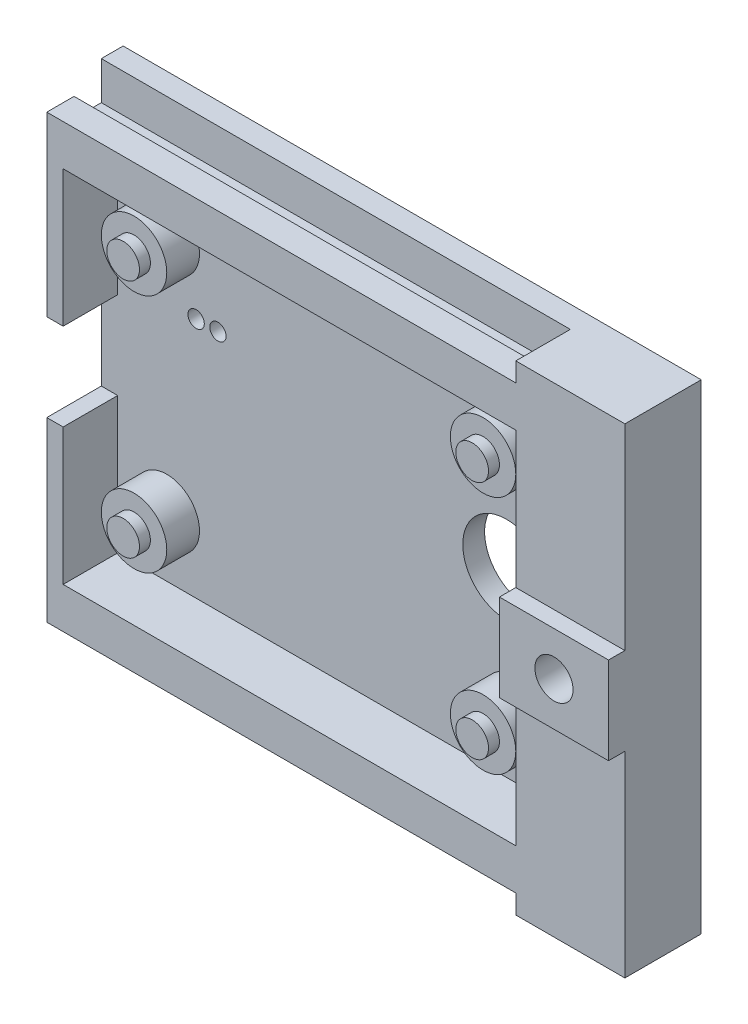
SolidWorks part; units mm, degrees
ref_plane "Alzado" through (0, 0, 0) normal (0, 0, 1) x (1, 0, 0)
ref_plane "Planta" through (0, 0, 0) normal (0, 1, 0) x (1, 0, 0)
ref_plane "Vista lateral" through (0, 0, 0) normal (1, 0, 0) x (0, 0, -1)
sketch "Croquis1" plane through (0, 0, 0) normal (0, 0, 1) x (1, 0, 0)
  line L0 (-22, 22) -> (-22, -22)
  line L1 (-22, -22) -> (31, -22)
  line L2 (31, -22) -> (31, 22)
  line L3 (31, 22) -> (-22, 22)
  line L13 (-20, 15) -> (20, 15) construction
  line L14 (-20, 15) -> (-20, -15) construction
  line L15 (-20, -15) -> (20, -15) construction
  line L16 (20, 15) -> (20, -15) construction
  line L17 (-20, 15) -> (20, -15) construction
  line L18 (-20, -15) -> (20, 15) construction
  circle A0 centre (-13.3084, 5.6686) radius 0.75
  circle A1 centre (-11.3084, 5.6686) radius 0.75
  circle A2 centre (15.1396, 0) radius 4
  point P0 (0, 0)
  point P3 (-22, 0)
  point P6 (15.1396, 0)
  point P8 (0, 0)
  dimension "D4" = 35.1396
  dimension "D9" = 2
  dimension "D10" = 1.5
  dimension "D3" = 8
  dimension "D1" = 44
  dimension "D2" = 2
  dimension "D6" = 40
  dimension "D7" = 30
  dimension "D8" = 11
  dimension "D11" = 6.6916
  dimension "D12" = 20.6686
extrude "Saliente-Extruir1" add sketch "Croquis1" along normal blind 2
sketch "Croquis4" plane through (0, 0, 2) normal (0, 0, 1) x (1, 0, 0)
  line L1 (-20, 15) -> (20, 15) construction
  line L2 (-20, 15) -> (-20, -15) construction
  line L3 (-20, -15) -> (20, -15) construction
  line L4 (20, 15) -> (20, -15) construction
  line L5 (-20, 15) -> (20, -15) construction
  line L6 (-20, -15) -> (20, 15) construction
  circle A0 centre (-16, -11) radius 1.5
  circle A1 centre (16, -11) radius 1.5
  circle A2 centre (16, 11) radius 1.5
  circle A3 centre (-16, 11) radius 1.5
  point P12 (0, 0)
  dimension "D1" = 3
  dimension "D2" = 30
  dimension "D3" = 40
  dimension "D4" = 4
  dimension "D5" = 4
  dimension "D6" = 4
  dimension "D7" = 4
extrude "Saliente-Extruir3" add sketch "Croquis4" along normal blind 4
sketch "Croquis5" plane through (0, 0, 0) normal (0, 0, -1) x (-1, 0, 0)
  line L0 (-31, -22) -> (-31, 22) construction
  circle A0 centre (-26, 0) radius 1.75
  dimension "D2" = 3.5
  dimension "D1" = 5
extrude "Cortar-Extruir1" cut sketch "Croquis5" against normal up to next
sketch "Croquis6" plane through (0, 0, 2) normal (0, 0, 1) x (1, 0, 0)
  line L0 (-22, -18.5) -> (21, -18.5)
  line L1 (-22, 22) -> (-22, -22) construction
  line L3 (-22, -18.5) -> (-22, 18.5)
  line L4 (-20.5, -16.5) -> (21, -16.5)
  line L7 (-20.5, 16.5) -> (21, 16.5)
  line L8 (-20.5, -16.5) -> (-20.5, 16.5)
  line L9 (21, 18.5) -> (-22, 18.5)
  line L11 (21, -18.5) -> (21, -22)
  line L12 (-22, -22) -> (31, -22) construction
  line L13 (21, -22) -> (31, -22)
  line L14 (31, -22) -> (31, 22)
  line L15 (31, 22) -> (21, 22)
  line L16 (31, 22) -> (-22, 22) construction
  line L17 (21, 22) -> (21, 18.5)
  line L18 (21, -16.5) -> (21, 16.5)
  circle A0 centre (26, 0) radius 1.75 construction
  circle A1 centre (26, 0) radius 1.75
  dimension "D1" = 37
  dimension "D2" = 2
  dimension "D3" = 2
  dimension "D4" = 18.5
  dimension "D5" = 43
  dimension "D6" = 1.5
extrude "Saliente-Extruir4" add sketch "Croquis6" along normal blind 5
sketch "Croquis7" plane through (0, 0, 7) normal (0, 0, 1) x (1, 0, 0)
  line L0 (-22, 18.5) -> (-22, 20.25)
  line L1 (-22, 22) -> (-22, 18.5) construction
  line L2 (-22, 20.25) -> (21, 20.25)
  line L3 (21, 22) -> (21, 18.5) construction
  line L4 (21, 20.25) -> (21, 18.5)
  line L5 (21, 18.5) -> (-22, 18.5)
  line L6 (-22, -18.5) -> (-22, -20.25)
  line L7 (-22, -18.5) -> (-22, -22) construction
  line L8 (-22, -20.25) -> (21, -20.25)
  line L9 (21, -18.5) -> (21, -22) construction
  line L10 (21, -20.25) -> (21, -18.5)
  line L11 (21, -18.5) -> (-22, -18.5)
extrude "Saliente-Extruir5" add sketch "Croquis7" against normal blind 2.5
sketch "Croquis8" plane through (0, 0, 7) normal (0, 0, 1) x (1, 0, 0)
  line L0 (-20.5, -4) -> (-20.5, 4)
  line L1 (-20.5, 16.5) -> (-20.5, -16.5) construction
  line L2 (-20.5, 4) -> (-22, 4)
  line L3 (-22, 20.25) -> (-22, -20.25) construction
  line L4 (-22, 4) -> (-22, -4)
  line L5 (-22, -4) -> (-20.5, -4)
  point P4 (-20.5, 0)
  dimension "D1" = 8
extrude "Cortar-Extruir3" cut sketch "Croquis8" against normal blind 5
sketch "Croquis9" plane through (0, 0, 0) normal (0, 0, -1) x (-1, 0, 0)
  circle A0 centre (-26, 0) radius 3.5
  dimension "D1" = 7
extrude "Cortar-Extruir4" cut sketch "Croquis9" against normal blind 5
sketch "Croquis10" plane through (0, 0, 2) normal (0, 0, 1) x (1, 0, 0)
  circle A0 centre (-16, 11) radius 3
  circle A1 centre (16, 11) radius 3
  circle A2 centre (16, -11) radius 3
  circle A3 centre (-16, -11) radius 3
  dimension "D1" = 6
extrude "Saliente-Extruir6" add sketch "Croquis10" along normal blind 3
sketch "Croquis12" plane through (0, 0, 7) normal (0, 0, 1) x (1, 0, 0)
  line L0 (21, -4) -> (21, 4)
  line L1 (21, -16.5) -> (21, 16.5) construction
  line L2 (21, -4) -> (31, -4)
  line L3 (31, -22) -> (31, 22) construction
  line L4 (31, -4) -> (31, 4)
  line L5 (31, 4) -> (21, 4)
  circle A0 centre (26, 0) radius 1.75 construction
  circle A1 centre (26, 0) radius 1.75
  point P4 (21, 0)
  dimension "D1" = 8
extrude "Saliente-Extruir7" add sketch "Croquis12" along normal blind 1.5
